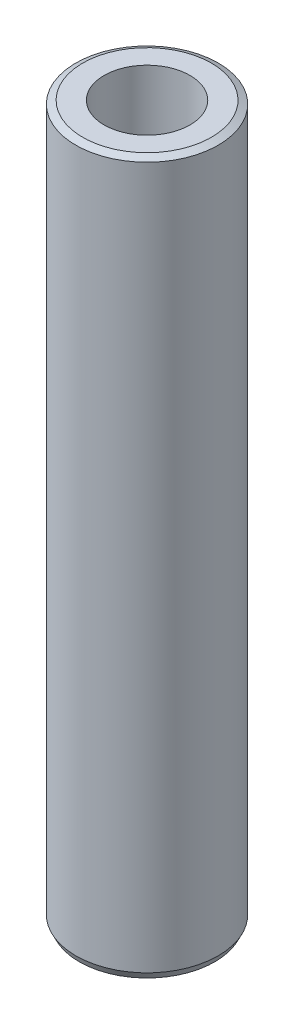
SolidWorks part; units mm, degrees
ref_plane "Front Plane" through (0, 0, 0) normal (0, 0, 1) x (1, 0, 0)
ref_plane "Top Plane" through (0, 0, 0) normal (0, 1, 0) x (1, 0, 0)
ref_plane "Right Plane" through (0, 0, 0) normal (1, 0, 0) x (0, 0, -1)
sketch "Sketch1" plane through (0, 0, 0) normal (0, 1, 0) x (1, 0, 0)
  circle A0 centre (0, 0) radius 60
  dimension "SHAFT_OD" = 120
extrude "Boss-Extrude1" add sketch "Sketch1" along normal blind 600
sketch "Sketch2" plane through (0, 0, 0) normal (0, 1, 0) x (1, 0, 0)
  circle A0 centre (0, 0) radius 36.1672
  dimension "BORE_D" = 72.3344
extrude "Cut-Extrude1" cut sketch "Sketch2" along normal through all
chamfer "Chamfer1" distance 2.848 angle 63.865 2 edges at (0, 600, 60) (0, 0, 60) first distance on face at (0, 600, 60) first distance on face at (0, 0, 36.1672)
